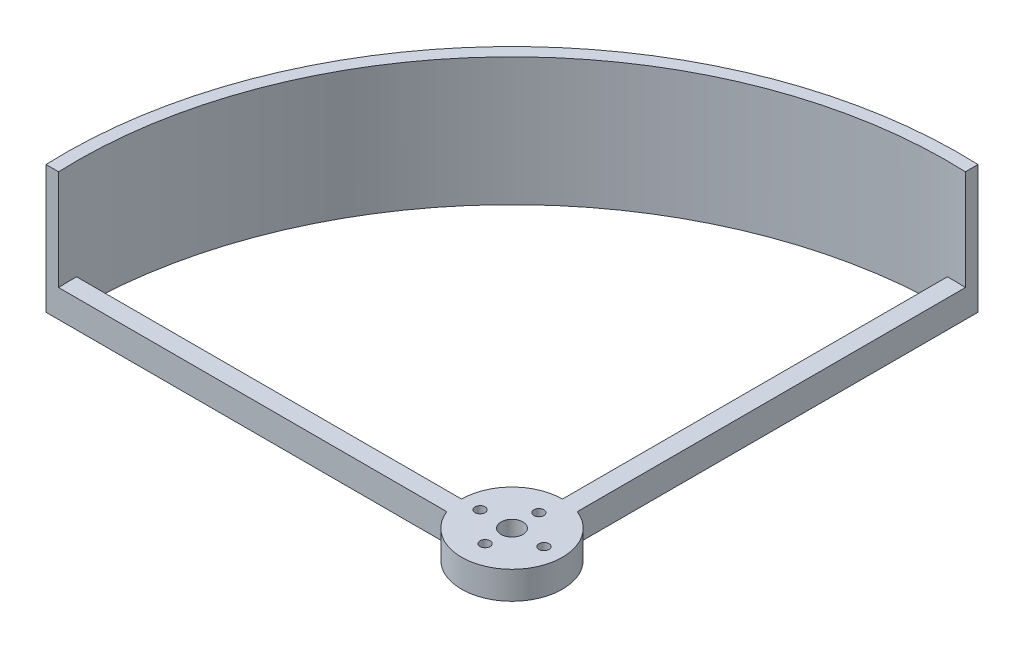
SolidWorks part; units mm, degrees
ref_plane "Front Plane" through (0, 0, 0) normal (0, 0, 1) x (1, 0, 0)
ref_plane "Top Plane" through (0, 0, 0) normal (0, 1, 0) x (1, 0, 0)
ref_plane "Right Plane" through (0, 0, 0) normal (1, 0, 0) x (0, 0, -1)
sketch "Sketch1" plane through (0, 0, 0) normal (0, 1, 0) x (1, 0, 0)
  line L0 (0, 129.6032) -> (0, 9.3426)
  line L1 (5.4516, 9.3426) -> (5.4516, 129.4885)
  line L2 (0, 0) -> (-22.0351, 22.0351) construction
  line L3 (-22.0351, 22.0351) -> (23.6345, -23.6345) construction
  line L4 (-9.3426, -5.4516) -> (-129.4885, -5.4516)
  line L5 (-129.6032, 0) -> (-9.3426, 0)
  line L6 (5.4516, 9.3426) -> (5.4516, 129.4885)
  line L7 (5.4516, 129.4885) -> (5.4516, 133.2385)
  line L8 (-129.4885, -5.4516) -> (-133.2385, -5.4516)
  circle A0 centre (0, 0) radius 15
  arc A1 (5.4516, 129.4885) -> (-129.4885, -5.4516) centre (0, 0) ccw
  arc A2 (5.4516, 133.2385) -> (-133.2385, -5.4516) centre (0, 0) ccw
  dimension "D1" = 30
  dimension "D2" = 133.35
extrude "Boss-Extrude2" add sketch "Sketch1" along normal blind 8.255 contours A0
extrude "Boss-Extrude3" add sketch "Sketch1<6>" along normal blind 8.255 contours L5 A1 L4 A0 | L6 A1 L0 A0 region at (2.7294, 0, -72.1136) region at (-72.1136, 0, 2.7294)
sketch "Sketch1<6>" plane through (0, 0, 0) normal (0, 1, 0) x (1, 0, 0) same geometry as "Sketch1"
extrude "Boss-Extrude4" add sketch "Sketch1<7>" along normal blind 38.1 contours L7 A2 L8 A1 region at (-93.0313, 0, -93.0313)
sketch "Sketch1<7>" plane through (0, 0, 0) normal (0, 1, 0) x (1, 0, 0) same geometry as "Sketch1"
ref_plane "Plane1" through (-62.0185, 0, -62.0185) normal (0.7071, 0, 0.7071) x (0.7071, 0, -0.7071)
sketch "Sketch5" plane through (0, 8.255, 0) normal (0, 1, 0) x (1, 0, 0)
  line L0 (0, 0) -> (29.635, 0) construction
  line L1 (0, 0) -> (0, 21.5427) construction
  line L2 (0, 129.6032) -> (0, 15) construction
  line L3 (0, 0) -> (29.22, 0) construction
  line L4 (21.3608, 0) -> (-27.7675, 0) construction
  line L5 (0, 0) -> (0, 21.6948) construction
  line L6 (0, 8) -> (0, 0) construction
  line L7 (0, 0) -> (45.7038, -54.4677) construction
  line L8 (0, 0) -> (-19.6346, 0) construction
  line L9 (-129.6032, 0) -> (-15, 0) construction
  circle A0 centre (-9.5, 0) radius 1.5
  circle A1 centre (0, 8) radius 1.5
  circle A2 centre (0, -8) radius 1.5
  circle A3 centre (9.5, 0) radius 1.5
  circle A6 centre (0, 0) radius 3.25
  point P18 (0, 0)
  dimension "D3" = 3
  dimension "D7" = 3
  dimension "D8" = 6.5
  dimension "D2" = 8
  dimension "D5" = 90
  dimension "D6" = 8
  dimension "D9" = 90
  dimension "D10" = 9.5
  dimension "D4" = 50
extrude "Cut-Extrude3" cut sketch "Sketch5" against normal blind 63.5
